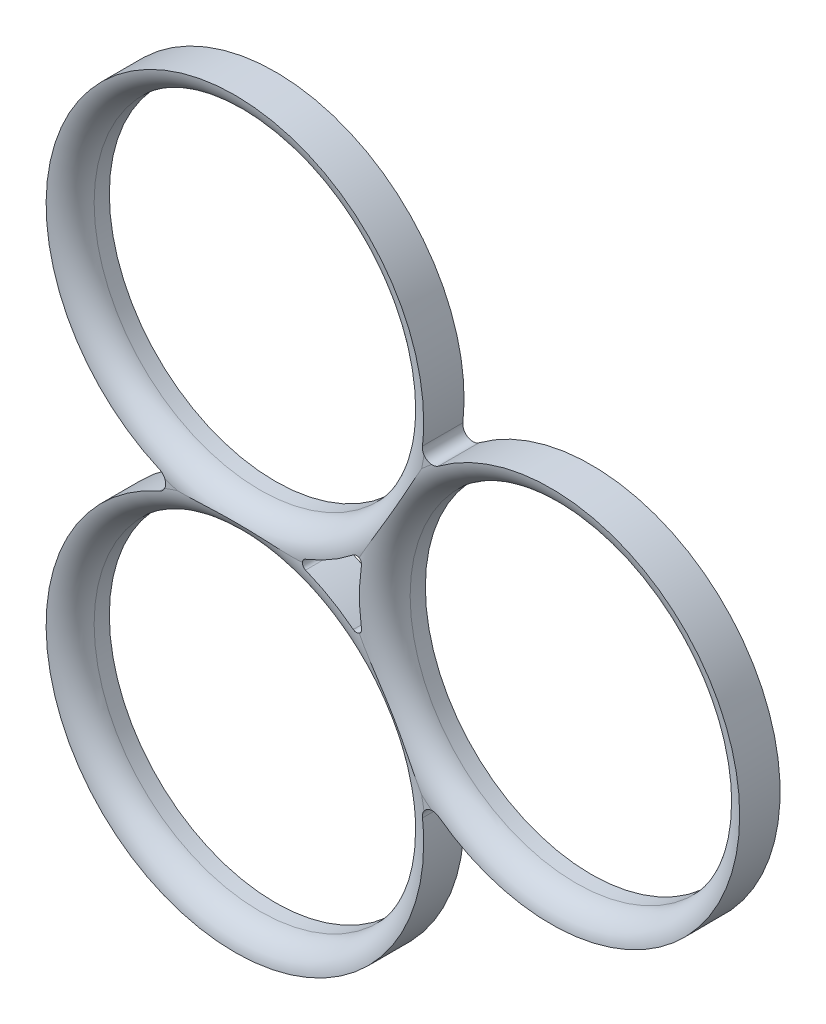
SolidWorks part; units mm, degrees
ref_plane "Front Plane" through (0, 0, 0) normal (1, 0, 0) x (0, 1, 0)
ref_plane "Top Plane" through (0, 0, 0) normal (0, 0, 1) x (0, 1, 0)
ref_plane "Right Plane" through (0, 0, 0) normal (0, 1, 0) x (-1, 0, 0)
ref_axis "x axis" through (-88.99, 0, 0) along (1, 0, 0)
ref_axis "y xxis" through (0, 88.99, 0) along (0, -1, 0)
ref_axis "z axis" through (0, 0, 55) along (0, 0, -1)
sketch "Sketch1" plane through (0, 0, 0) normal (0, 0, 1) x (0, 1, 0)
  line L0 (0, 0) -> (0, -41.5692) construction
  line L1 (0, 0) -> (-36, 20.7846) construction
  line L2 (0, 0) -> (36, 20.7846) construction
  line L3 (-36, 20.7846) -> (0, -41.5692) construction
  line L4 (0, -41.5692) -> (36, 20.7846) construction
  line L5 (36, 20.7846) -> (-36, 20.7846) construction
  dimension "D1" = 72
sketch "Sketch2" plane through (0, 0, 0) normal (0, 0, 1) x (0, 1, 0)
  circle A0 centre (-36, 20.7846) radius 32.75
  circle A1 centre (36, 20.7846) radius 32.75
  circle A2 centre (0, -41.5692) radius 32.75
  arc A3 (0, 30.3534) -> (-26.2868, -15.1767) centre (-36, 20.7846) ccw
  arc A4 (26.2868, -15.1767) -> (0, 30.3534) centre (36, 20.7846) ccw
  arc A5 (-26.2868, -15.1767) -> (26.2868, -15.1767) centre (0, -41.5692) ccw
  circle A6 centre (-36, 20.7846) radius 37.25 construction
  circle A7 centre (-36, 20.7846) radius 32.75 construction
  circle A8 centre (36, 20.7846) radius 37.25 construction
  circle A9 centre (36, 20.7846) radius 32.75 construction
  circle A10 centre (0, -41.5692) radius 37.25 construction
  circle A11 centre (0, -41.5692) radius 32.75 construction
  point P33 (0, 0)
  dimension "D1" = 65.5
  dimension "D2" = 4.5
extrude "Boss-Extrude1" add sketch "Sketch2" along normal blind 8
fillet "Fillet1" radius 2 3 edges at (-30.3534, 0, 4) (15.1767, 26.2868, 4) (15.1767, -26.2868, 4)
fillet "Fillet3" radius 5 3 edges at (11.9654, 36, 8) (74.3192, 0, 8) (11.9654, -36, 8)
sketch "Sketch3" plane through (0, 0, 8) normal (0, 0, 1) x (1, 0, 0)
  arc A6 (4.712, 8.1615) -> (4.712, -8.1615) centre (41.5692, 0) ccw
  arc A8 (4.712, 8.1615) -> (4.712, -8.1615) centre (41.5692, 0) ccw
  arc A13 (-9.424, 0) -> (4.712, 8.1615) centre (-20.7846, 36) ccw
  arc A15 (-9.424, 0) -> (4.712, 8.1615) centre (-20.7846, 36) ccw
  arc A16 (4.712, -8.1615) -> (-9.424, 0) centre (-20.7846, -36) ccw
  arc A17 (4.712, -8.1615) -> (-9.424, 0) centre (-20.7846, -36) ccw
  dimension "D1" = 0
extrude "Cut-Extrude1" cut sketch "Sketch3" against normal blind 10
fillet "Fillet4" radius 1 3 edges at (4.712, 8.1615, 4) (4.712, -8.1615, 4) (-9.424, 0, 4)
